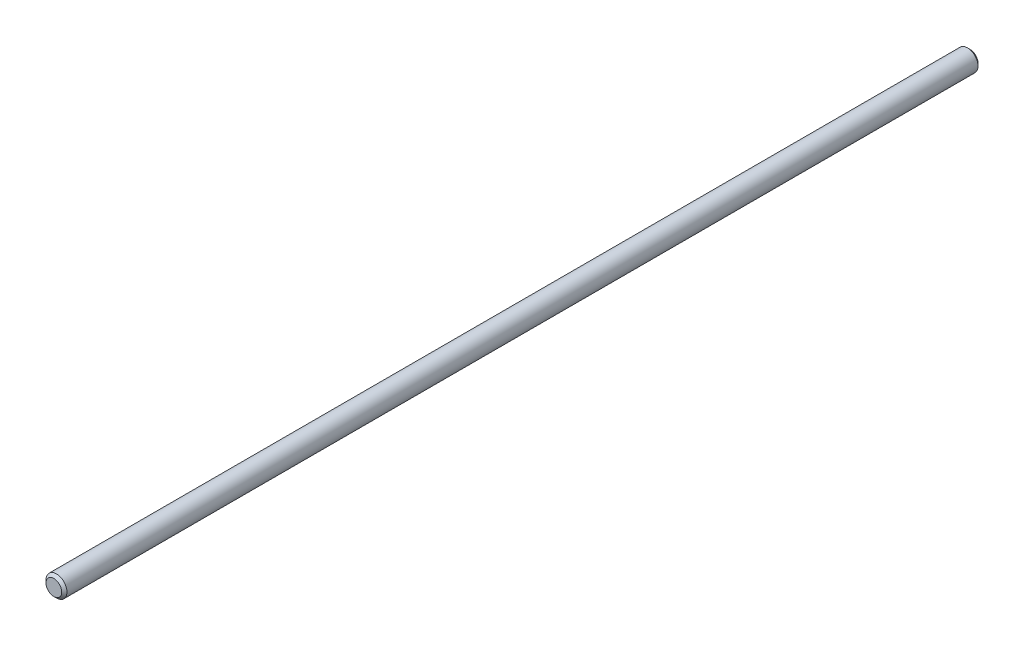
SolidWorks part; units mm, degrees
ref_plane "Piano frontale" through (0, 0, 0) normal (0, 0, 1) x (1, 0, 0)
ref_plane "Piano superiore" through (0, 0, 0) normal (0, 1, 0) x (1, 0, 0)
ref_plane "Piano destro" through (0, 0, 0) normal (1, 0, 0) x (0, 0, -1)
sketch "Schizzo1" plane through (0, 0, 0) normal (0, 0, 1) x (1, 0, 0)
  circle A0 centre (0, 0) radius 4
  dimension "D1" = 8
extrude "Estrusione-Estrusione1" add sketch "Schizzo1" along normal blind 350
chamfer "Smusso1" distance 1 angle 45 2 edges at (4, 0, 350) (4, 0, 0)
